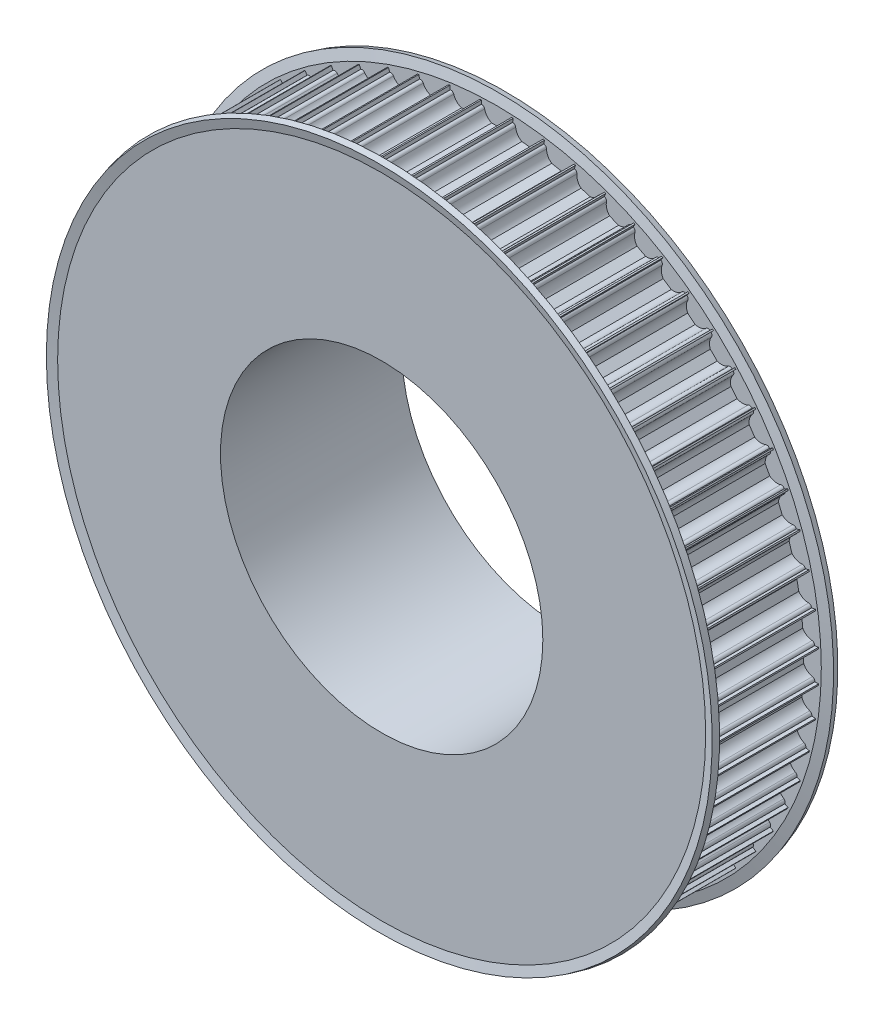
SolidWorks part; units mm, degrees
ref_plane "Front Plane" through (0, 0, 0) normal (0, 0, 1) x (1, 0, 0)
ref_plane "Top Plane" through (0, 0, 0) normal (0, 1, 0) x (1, 0, 0)
ref_plane "Right Plane" through (0, 0, 0) normal (1, 0, 0) x (0, 0, -1)
sketch "Sketch1" plane through (0, 0, 0) normal (1, 0, 0) x (0, 0, -1)
  line L0 (0, 0) -> (61.9374, 0) construction
  line L1 (0, 40) -> (0, 80)
  line L2 (0, 80) -> (30, 80)
  line L3 (30, 80) -> (30, 55.5)
  line L4 (30, 55.5) -> (45, 55.5)
  line L5 (45, 55.5) -> (45, 40)
  line L6 (45, 40) -> (0, 40)
  dimension "D1" = 80
  dimension "D2" = 30
  dimension "D3" = 15
  dimension "D4" = 40
  dimension "D5" = 15.5
revolve "Revolve1" add sketch "Sketch1" angle 360 about L0
sketch "Sketch2" plane through (0, 0, 0) normal (0, 0, 1) x (1, 0, 0)
  line L0 (-3.6742, 79) -> (-3.75, 79)
  line L1 (-3.75, 79) -> (-3.75, 81)
  line L2 (-3.75, 81) -> (3.75, 81)
  line L3 (3.75, 81) -> (3.75, 79)
  line L4 (3.75, 79) -> (3.6742, 79)
  line L5 (1.199, 76.25) -> (-1.199, 76.25)
  arc A0 (2.9394, 78.4) -> (1.199, 76.25) centre (0, 79) cw
  arc A1 (2.9394, 78.4) -> (3.6742, 79) centre (3.6742, 78.25) cw
  arc A2 (-2.9394, 78.4) -> (-3.6742, 79) centre (-3.6742, 78.25) ccw
  arc A3 (-1.199, 76.25) -> (-2.9394, 78.4) centre (0, 79) cw
  point P10 (3, 79)
  point P13 (-3, 79)
  dimension "D1" = 3
  dimension "D6" = 0.75
  dimension "D2" = 79
  dimension "D3" = 7.5
  dimension "D4" = 2
  dimension "D5" = 3.75
  dimension "D7" = 2.75
extrude "Cut-Extrude1" cut sketch "Sketch2" against normal up to next
pattern_circular "CirPattern1" count 64 over 360 about axis through (0, 0, 0) along (0, 0, 1) of "Cut-Extrude1"
sketch "Sketch3" plane through (0, 0, 0) normal (1, 0, 0) x (0, 0, -1)
  line L0 (15, -3.6742) -> (15, -40.9775) construction
  line L1 (30, -3.6742) -> (0, -3.6742) construction
  line L2 (30, -40.9775) -> (0, -40.9775) construction
  line L3 (30, 55.5) -> (30, 80.4125)
  line L4 (30, 80.4125) -> (30.592, 82.6218)
  line L5 (30.592, 82.6218) -> (29.1431, 83.01)
  line L6 (29.1431, 83.01) -> (28.5, 80.61)
  line L7 (28.5, 80.61) -> (28.5, 55.5)
  line L8 (28.5, 55.5) -> (30, 55.5)
  line L9 (45, 55.5) -> (30, 55.5) construction
  line L10 (1.5, 80.61) -> (1.5, 55.5)
  line L11 (0.8569, 83.01) -> (1.5, 80.61)
  line L12 (-0.592, 82.6218) -> (0.8569, 83.01)
  line L13 (0, 80.4125) -> (-0.592, 82.6218)
  line L14 (0, 55.5) -> (0, 80.4125)
  line L15 (1.5, 55.5) -> (0, 55.5)
  line L16 (0, 0) -> (-13.4738, 0) construction
  dimension "D1" = 15
  dimension "D2" = 1.5
  dimension "D3" = 25.11
  dimension "D4" = 2.4
  dimension "D5" = 1.5
revolve "Revolve2" add sketch "Sketch3" angle 360 about L16
